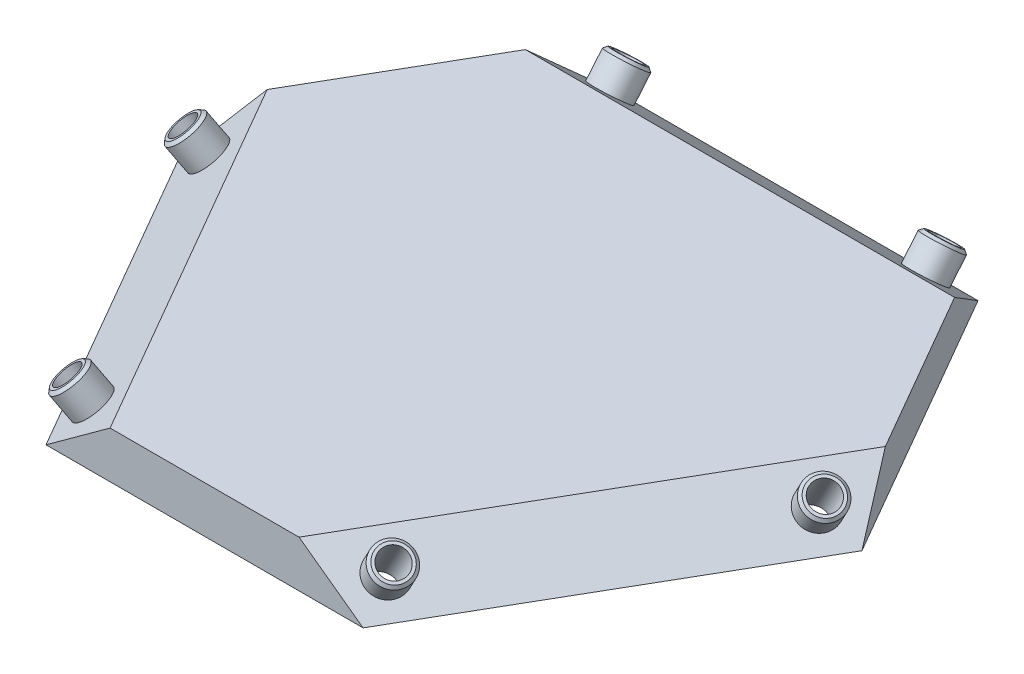
SolidWorks part; units mm, degrees
ref_plane "Front Plane" through (0, 0, 0) normal (0, 0, 1) x (1, 0, 0)
ref_plane "Top Plane" through (0, 0, 0) normal (0, 1, 0) x (1, 0, 0)
ref_plane "Right Plane" through (0, 0, 0) normal (1, 0, 0) x (0, 0, -1)
sketch "Sketch1" plane through (0, 0, 0) normal (0, 1, 0) x (1, 0, 0)
  line L7 (-60, 0) -> (-30, -51.9615)
  line L8 (-30, -51.9615) -> (30, -51.9615)
  line L9 (30, -51.9615) -> (60, 0)
  line L10 (60, 0) -> (30, 51.9615)
  line L11 (30, 51.9615) -> (-30, 51.9615)
  line L12 (-30, 51.9615) -> (-60, 0)
  circle A1 centre (0, 0) radius 51.9615 construction
  dimension "D1" = 60
extrude "Boss-Extrude1" add sketch "Sketch1" along normal blind 8
chamfer "Chamfer1" distance 10 angle 50 3 edges at (0, 8, -51.9615) (-45, 8, 25.9808) (45, 8, 25.9808) first distance on face at (0, 4, -51.9615) first distance on face at (-45, 4, 25.9808) first distance on face at (45, 4, 25.9808)
sketch "Sketch4" plane through (17.74, 24.4124, 10.2422) normal (0.5567, 0.766, 0.3214) x (0.8301, -0.4979, -0.251)
  line L0 (46.1828, 6.3514) -> (3.0135, -46.52) construction
  line L1 (9.5744, -48.3238) -> (-3.5474, -44.7162) construction
  line L2 (43.1032, 12.419) -> (49.2624, 0.2838) construction
  circle A0 centre (41.7556, 0.9292) radius 2.3
  circle A1 centre (7.4407, -41.0978) radius 2.3
  dimension "D1" = 4.6
  dimension "D2" = 7
  dimension "D3" = 7
sketch "Sketch6" plane through (-17.74, 24.4124, 10.2422) normal (-0.5567, 0.766, 0.3214) x (0.8307, 0.5133, 0.2154)
  line L0 (-45.9011, 8.1412) -> (-4.8189, -46.3678) construction
  line L1 (1.8071, -44.8203) -> (-11.445, -47.9153) construction
  line L2 (-49.2141, 2.1979) -> (-42.5881, 14.0846) construction
  circle A0 centre (-41.688, 2.5511) radius 2.3
  circle A1 centre (-9.0321, -40.7777) radius 2.3
  dimension "D1" = 4.6
  dimension "D2" = 7
  dimension "D3" = 7
sketch "Sketch7" plane through (0, 24.4124, -20.4844) normal (0, 0.766, -0.6428) x (1, 0, 0)
  line L0 (34.1284, 31.7561) -> (-34.1284, 31.7561) construction
  line L1 (-36.8806, 25.5332) -> (-31.3761, 37.979) construction
  line L2 (31.3761, 37.979) -> (36.8806, 25.5332) construction
  circle A0 centre (-27.1284, 31.7561) radius 2.3
  circle A1 centre (27.1284, 31.7561) radius 2.3
  dimension "D1" = 4.6
  dimension "D2" = 7
  dimension "D3" = 7
extrude "Cut-Extrude1" cut sketch "Sketch4" against normal through all
extrude "Cut-Extrude2" cut sketch "Sketch7" against normal through all
extrude "Cut-Extrude3" cut sketch "Sketch6" against normal through all
sketch "Sketch8" plane through (17.74, 24.4124, 10.2422) normal (0.5567, 0.766, 0.3214) x (0.8307, -0.5133, -0.2154)
  circle A0 centre (9.0321, -40.7777) radius 3.3
  circle A1 centre (9.0321, -40.7777) radius 2.3
  circle A2 centre (41.688, 2.5511) radius 2.3
  circle A3 centre (41.688, 2.5511) radius 3.3
  dimension "D1" = 1
  dimension "D2" = 1
extrude "Boss-Extrude2" add sketch "Sketch8" along normal blind 5
sketch "Sketch9" plane through (-17.74, 24.4124, 10.2422) normal (-0.5567, 0.766, 0.3214) x (0.8307, 0.5133, 0.2154)
  circle A0 centre (-41.688, 2.5511) radius 2.3
  circle A1 centre (-41.688, 2.5511) radius 3.3
  circle A2 centre (-9.0321, -40.7777) radius 2.3
  circle A3 centre (-9.0321, -40.7777) radius 3.3
  dimension "D1" = 1
  dimension "D2" = 1
extrude "Boss-Extrude3" add sketch "Sketch9" along normal blind 5
sketch "Sketch10" plane through (0, 24.4124, -20.4844) normal (0, 0.766, -0.6428) x (1, 0, 0)
  circle A0 centre (-27.1284, 31.7561) radius 2.3
  circle A1 centre (-27.1284, 31.7561) radius 3.3
  circle A2 centre (27.1284, 31.7561) radius 2.3
  circle A3 centre (27.1284, 31.7561) radius 3.3
  dimension "D1" = 1
  dimension "D2" = 1
extrude "Boss-Extrude4" add sketch "Sketch10" along normal blind 5
chamfer "Chamfer2" distance 0.5 angle 45 6 edges at (-27.1284, 9.9514, -45.497) (27.1284, 9.9514, -45.497) (52.4854, 9.7702, 0.5186) (25.3571, 9.7702, 47.5063) (-30.6962, 5.8903, 47.5063) (-57.8246, 5.8903, 0.5186)
equation "\"`9\"=8"
